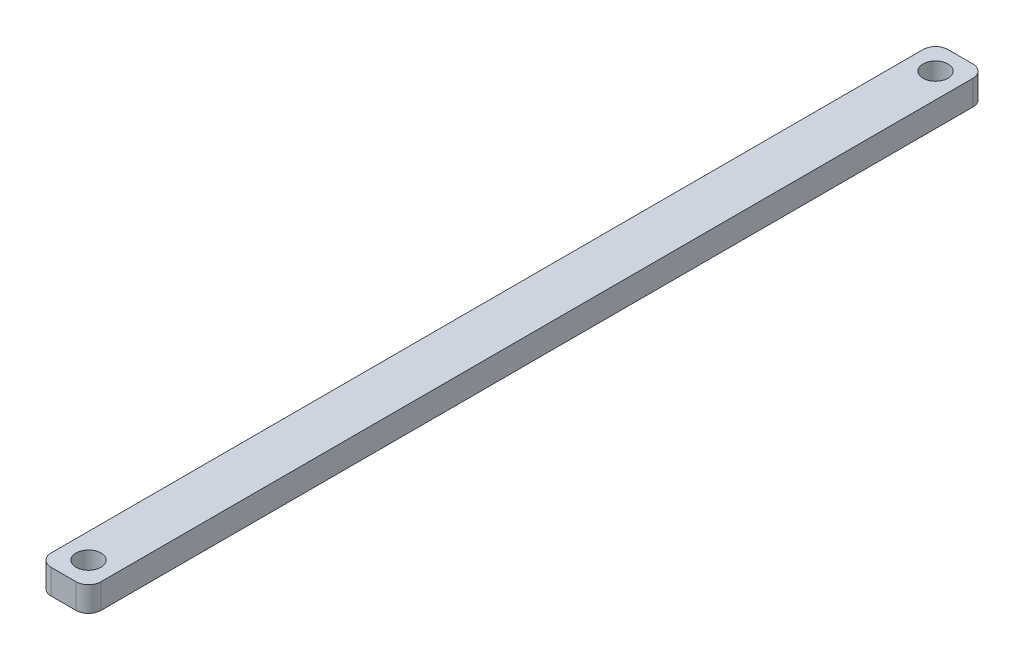
SolidWorks part; units mm, degrees
ref_plane "Front Plane" through (0, 0, 0) normal (0, 0, 1) x (1, 0, 0)
ref_plane "Top Plane" through (0, 0, 0) normal (0, 1, 0) x (1, 0, 0)
ref_plane "Right Plane" through (0, 0, 0) normal (1, 0, 0) x (0, 0, -1)
sketch "Sketch1" plane through (0, 0, 0) normal (0, 1, 0) x (1, 0, 0)
  line L1 (-12.7, -228.6) -> (12.7, -228.6)
  line L2 (-12.7, -228.6) -> (-12.7, 228.6)
  line L3 (-12.7, 228.6) -> (12.7, 228.6)
  line L4 (12.7, -228.6) -> (12.7, 228.6)
  line L5 (-12.7, -228.6) -> (12.7, 228.6) construction
  line L6 (-12.7, 228.6) -> (12.7, -228.6) construction
  point P0 (0, 0)
  dimension "D1" = 25.4
  dimension "D2" = 457.2
extrude "Boss-Extrude1" add sketch "Sketch1" along normal mid plane 12.7
fillet "Fillet1" radius 6.35 4 edges at (12.7, 0, -228.6) (-12.7, 0, -228.6) (12.7, 0, 228.6) (-12.7, 0, 228.6)
sketch "Sketch2" plane through (0, 6.35, 0) normal (0, 1, 0) x (1, 0, 0)
  line L0 (0, 215.9) -> (0, 228.6) construction
  line L1 (6.35, 228.6) -> (-6.35, 228.6) construction
  circle A0 centre (0, 215.9) radius 6.35
  dimension "D2" = 12.7
  dimension "D1" = 12.7
extrude "Cut-Extrude1" cut sketch "Sketch2" against normal through all
mirror "Mirror2" about plane through (0, 0, 0) normal (0, 0, 1) of "Cut-Extrude1"
